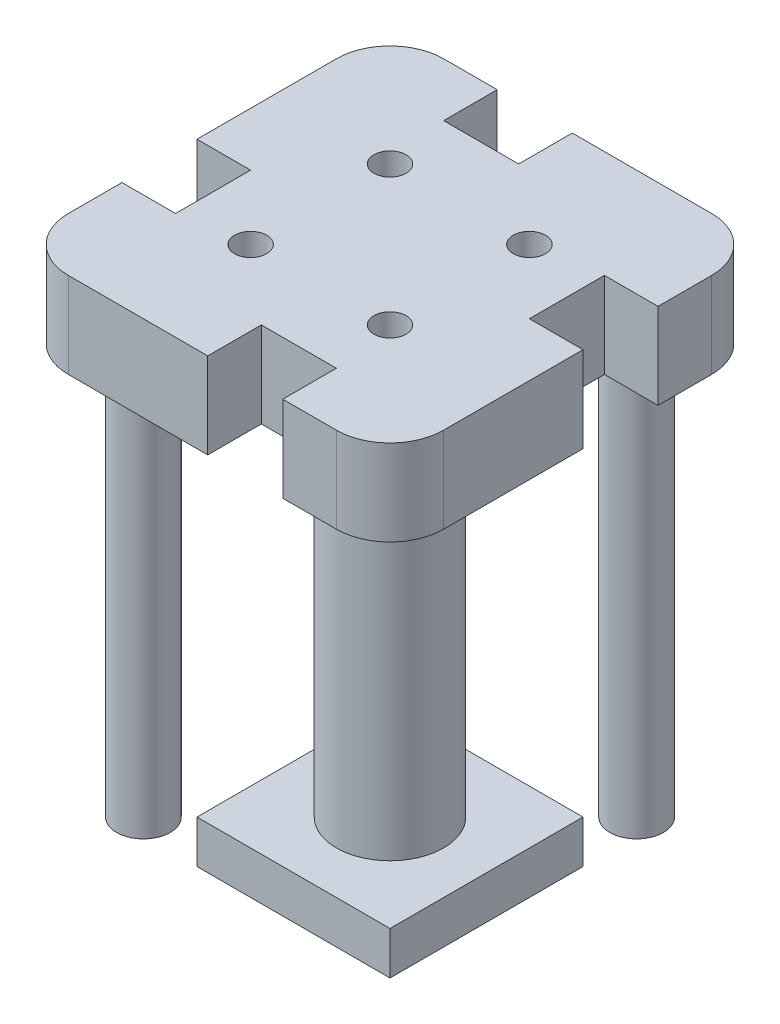
SolidWorks part; units mm, degrees
ref_plane "Front Plane" through (0, 0, 0) normal (0, 0, 1) x (1, 0, 0)
ref_plane "Top Plane" through (0, 0, 0) normal (0, 1, 0) x (1, 0, 0)
ref_plane "Right Plane" through (0, 0, 0) normal (1, 0, 0) x (0, 0, -1)
sketch "Sketch1" plane through (0, 0, 0) normal (0, 1, 0) x (1, 0, 0)
  line L1 (0, 0) -> (35, 0)
  line L2 (0, 0) -> (0, 35)
  line L3 (0, 35) -> (35, 35)
  line L4 (35, 0) -> (35, 35)
  dimension "D1" = 35
  dimension "D2" = 35
extrude "Boss-Extrude1" add sketch "Sketch1" along normal blind 8
sketch "Sketch2" plane through (0, 0, 0) normal (0, -1, 0) x (1, 0, 0)
  line L0 (0, 0) -> (35, 0) construction
  line L1 (18, 0) -> (25, 0)
  line L2 (18, 0) -> (18, -5)
  line L3 (18, -5) -> (25, -5)
  line L4 (25, 0) -> (25, -5)
  line L5 (35, -35) -> (0, -35) construction
  line L6 (10, -35) -> (17, -35)
  line L7 (10, -35) -> (10, -30)
  line L8 (10, -30) -> (17, -30)
  line L9 (17, -35) -> (17, -30)
  line L10 (0, -35) -> (0, 0) construction
  line L11 (0, -10) -> (5, -10)
  line L12 (0, -10) -> (0, -17)
  line L13 (0, -17) -> (5, -17)
  line L14 (5, -10) -> (5, -17)
  line L15 (35, 0) -> (35, -35) construction
  line L16 (35, -18) -> (30, -18)
  line L17 (35, -18) -> (35, -25)
  line L18 (35, -25) -> (30, -25)
  line L19 (30, -18) -> (30, -25)
  circle A0 centre (6, -6) radius 2.5
  circle A1 centre (29, -6) radius 4
  circle A2 centre (6, -29) radius 4
  circle A3 centre (29, -29) radius 2.5
  circle A4 centre (17.5, -17.5) radius 5
  circle A5 centre (11, -11) radius 1.5
  circle A6 centre (24, -11) radius 1.5
  circle A7 centre (24, -24) radius 1.5
  circle A8 centre (11, -24) radius 1.5
  point P45 (17.5, 0)
  point P46 (35, -17.5)
  line M26 (0, 0) -> (0, -35)
  line M27 (0, -35) -> (35, -35)
  line M28 (35, -35) -> (35, 0)
  line M29 (35, 0) -> (0, 0)
  dimension "D7" = 5
  dimension "D8" = 5
  dimension "D9" = 8
  dimension "D10" = 8
  dimension "D11" = 10
  dimension "D12" = 3
  dimension "D13" = 3
  dimension "D14" = 3
  dimension "D15" = 3
  dimension "D1" = 5
  dimension "D2" = 7
  dimension "D3" = 10
  dimension "D4" = 10
  dimension "D5" = 10
  dimension "D6" = 10
  dimension "D16" = 6
  dimension "D17" = 6
  dimension "D18" = 6
  dimension "D19" = 6
  dimension "D20" = 6
  dimension "D21" = 6
  dimension "D22" = 6
  dimension "D23" = 11
  dimension "D24" = 6
  dimension "D25" = 11
extrude "Cut-Extrude1" cut sketch "Sketch2" against normal through all contours L16 L19 L18 M28 | L9 L8 L7 M27 | L14 L11 L13 M26 | L4 L2 L3 M29 | A5 | A6 | A8 | A7 region at (21.5, 0, -2.5) region at (2.5, 0, -13.5) region at (32.5, 0, -21.5) region at (13.5, 0, -32.5) region at (11, 0, -11) region at (24, 0, -11) region at (24, 0, -24) region at (11, 0, -24)
extrude "Cut-Extrude2" cut sketch "Sketch2<5>" against normal blind 4 contours A2 | A1 | A5 region at (6, 0, -29)
sketch "Sketch2<5>" plane through (0, 0, 0) normal (0, -1, 0) x (1, 0, 0) same geometry as "Sketch2"
extrude "Boss-Extrude2" add sketch "Sketch2<7>" along normal blind 38.25 contours A4 | A3 | A0 region at (29, 0, -29) region at (17.5, 0, -17.5)
sketch "Sketch2<7>" plane through (0, 0, 0) normal (0, -1, 0) x (1, 0, 0) same geometry as "Sketch2"
sketch "Sketch3" plane through (0, -38.25, 0) normal (0, -1, 0) x (-1, 0, 0)
  line L0 (0, 10) -> (0, 0) construction
  line L1 (-8.5, 8.5) -> (-26.5, 8.5)
  line L2 (-8.5, 8.5) -> (-8.5, 26.5)
  line L3 (-8.5, 26.5) -> (-26.5, 26.5)
  line L4 (-26.5, 8.5) -> (-26.5, 26.5)
  line L5 (-25, 0) -> (-35, 0) construction
  line L6 (-35, 0) -> (-35, 18) construction
  line L7 (-35, 35) -> (-17, 35) construction
  dimension "D1" = 8.5
  dimension "D2" = 8.5
  dimension "D3" = 8.5
  dimension "D4" = 8.5
extrude "Boss-Extrude3" add sketch "Sketch3" along normal blind 4
fillet "Fillet1" radius 5 4 edges at (35, 4, -35) (0, 4, -35) (0, 4, 0) (35, 4, 0)
